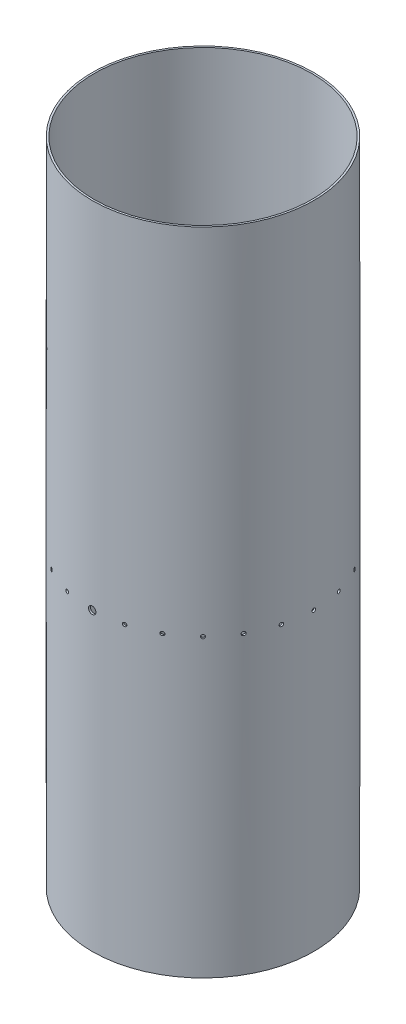
SolidWorks part; units mm, degrees
ref_plane "Front Plane" through (0, 0, 0) normal (0, 0, 1) x (1, 0, 0)
ref_plane "Top Plane" through (0, 0, 0) normal (0, 1, 0) x (1, 0, 0)
ref_plane "Right Plane" through (0, 0, 0) normal (1, 0, 0) x (0, 0, -1)
sketch "Sketch1" plane through (0, 0, 0) normal (0, 1, 0) x (1, 0, 0)
  circle A0 centre (0, 0) radius 95.25
  circle A1 centre (0, 0) radius 93.6625
  dimension "D1" = 190.5
  dimension "D2" = 187.325
extrude "Boss-Extrude1" add sketch "Sketch1" along normal blind 558.8
ref_plane "Plane1" through (0, 0, 88.9) normal (0, 0, 1) x (1, 0, 0)
sketch "Sketch10" plane through (0, 0, 88.9) normal (0, 0, 1) x (1, 0, 0)
  line L0 (95.25, 558.8) -> (-95.25, 558.8) construction
  circle A0 centre (0, 254) radius 1.5875
  dimension "D1" = 3.175
  dimension "D2" = 304.8
extrude "Cut-Extrude1" cut sketch "Sketch10" against normal through all
ref_axis "Axis1" through (0, 558.8, 0) along (0, -1, 0)
pattern_circular "CirPattern1" count 24 over 360 about axis through (0, 558.8, 0) along (0, -1, 0) of "Cut-Extrude1"
sketch "Sketch12" plane through (0, 0, 88.9) normal (0, 0, 1) x (1, 0, 0)
  circle A0 centre (0, 254) radius 3.175
  dimension "D1" = 6.35
extrude "Cut-Extrude2" cut sketch "Sketch12" against normal through all both and the other way through all
ref_axis "Axis2" through (0, 254, 93.4296) along (0, 0, 1)
sketch "Sketch16" plane through (0, 0, 0) normal (0, 0, 1) x (1, 0, 0)
  line L0 (0, 558.8) -> (0, 0) construction
  line L1 (97.79, 0) -> (-97.79, 0) construction
  circle A0 centre (-63.5, 406.4) radius 2.0955
  dimension "D1" = 4.191
  dimension "D2" = 63.5
  dimension "D3" = 406.4
extrude "Cut-Extrude5" cut sketch "Sketch16" against normal through all both and the other way through all
